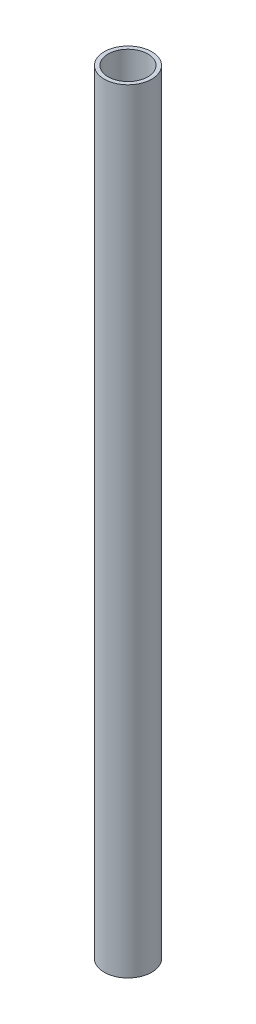
SolidWorks part; units mm, degrees
ref_plane "Alzado" through (0, 0, 0) normal (0, 0, 1) x (1, 0, 0)
ref_plane "Planta" through (0, 0, 0) normal (0, 1, 0) x (1, 0, 0)
ref_plane "Vista lateral" through (0, 0, 0) normal (1, 0, 0) x (0, 0, -1)
sketch "Croquis2" plane through (0, 0, 0) normal (0, 1, 0) x (1, 0, 0)
  circle A1 centre (0, 0) radius 8.14
  point P2 (0, 0)
  dimension "D1" = 16.28
extrude "Saliente-Extruir3" add sketch "Croquis2" along normal mid plane 265
sketch "Croquis5" plane through (0, 0, 0) normal (0, 1, 0) x (1, 0, 0)
  circle A0 centre (0, 0) radius 6.8
  dimension "D1" = 13.6
extrude "Cortar-Extruir1" cut sketch "Croquis5" along normal blind 459 and the other way blind 300
